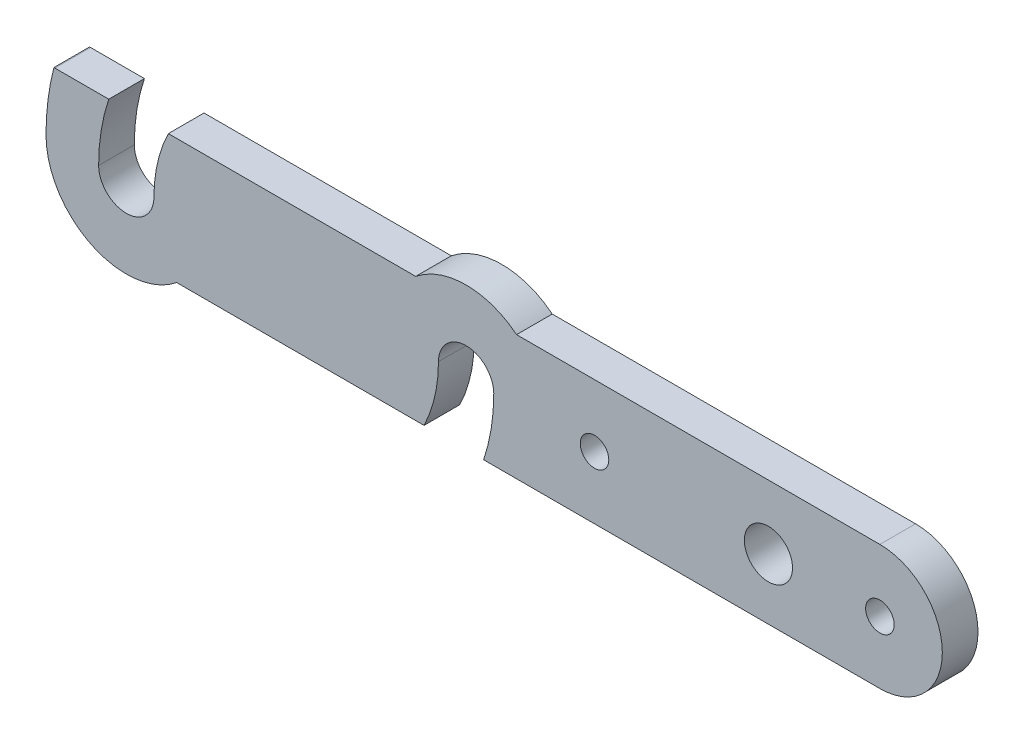
SolidWorks part; units mm, degrees
ref_plane "Front Plane" through (0, 0, 0) normal (0, 0, 1) x (1, 0, 0)
ref_plane "Top Plane" through (0, 0, 0) normal (0, 1, 0) x (1, 0, 0)
ref_plane "Right Plane" through (0, 0, 0) normal (1, 0, 0) x (0, 0, -1)
sketch "Sketch1" plane through (0, 0, 0) normal (0, 0, 1) x (1, 0, 0)
  line L1 (33.3761, 4) -> (74.1126, 4)
  line L2 (23.0014, -10) -> (-4.7289, -10)
  line L5 (29.6842, -10) -> (74.1126, -10)
  line L6 (-5.6679, 4) -> (22.0624, 4)
  line L8 (30.8193, -3) -> (74.1126, -3) construction
  line L9 (-25.3857, -3) -> (27.7193, -3) construction
  line L10 (-18.3857, 4) -> (-12.3507, 4)
  arc A0 (-13.4857, -3) -> (-7.2857, -3) centre (-10.3857, -3) ccw
  arc A1 (30.8193, -3) -> (24.6193, -3) centre (27.7193, -3) ccw
  circle A2 centre (61.614, -3.1883) radius 2.7
  arc A3 (-18.4986, 3.9991) -> (-18.3857, 4) centre (-18.3857, -3) cw
  arc A4 (-5.6679, 4) -> (-7.2857, -3) centre (8.6668, -3) ccw
  arc A5 (29.6842, -10) -> (30.8193, -3) centre (8.6668, -3) ccw
  arc A6 (23.0014, -10) -> (24.6193, -3) centre (8.6668, -3) ccw
  arc A7 (-12.3507, 4) -> (-13.4857, -3) centre (8.6668, -3) ccw
  arc A8 (33.3761, 4) -> (22.0624, 4) centre (27.7193, -3) ccw
  circle A9 centre (74.1126, -3) radius 1.6
  circle A10 centre (42.1149, -3) radius 1.6
  arc A11 (74.1126, -10) -> (74.1126, 4) centre (74.1126, -3) ccw
  arc A12 (-19.3857, -3) -> (-4.7289, -10) centre (-10.3857, -3) ccw
  arc A13 (-18.4986, 3.9991) -> (-19.3857, -3) centre (8.6668, -3) ccw
  arc A14 (-17.9484, 5.8643) -> (-19.3857, -3) centre (8.6668, -3) ccw construction
  dimension "D1" = 3.1
  dimension "D2" = 5.4
  dimension "D5" = 9
  dimension "D8" = 19.5
  dimension "D10" = 3.2
  dimension "D11" = 7
  dimension "D7" = 12.5
  dimension "D3" = 38.105
  dimension "D4" = 8
  dimension "D9" = 72
extrude "Boss-Extrude1" add sketch "Sketch1" along normal blind 4
